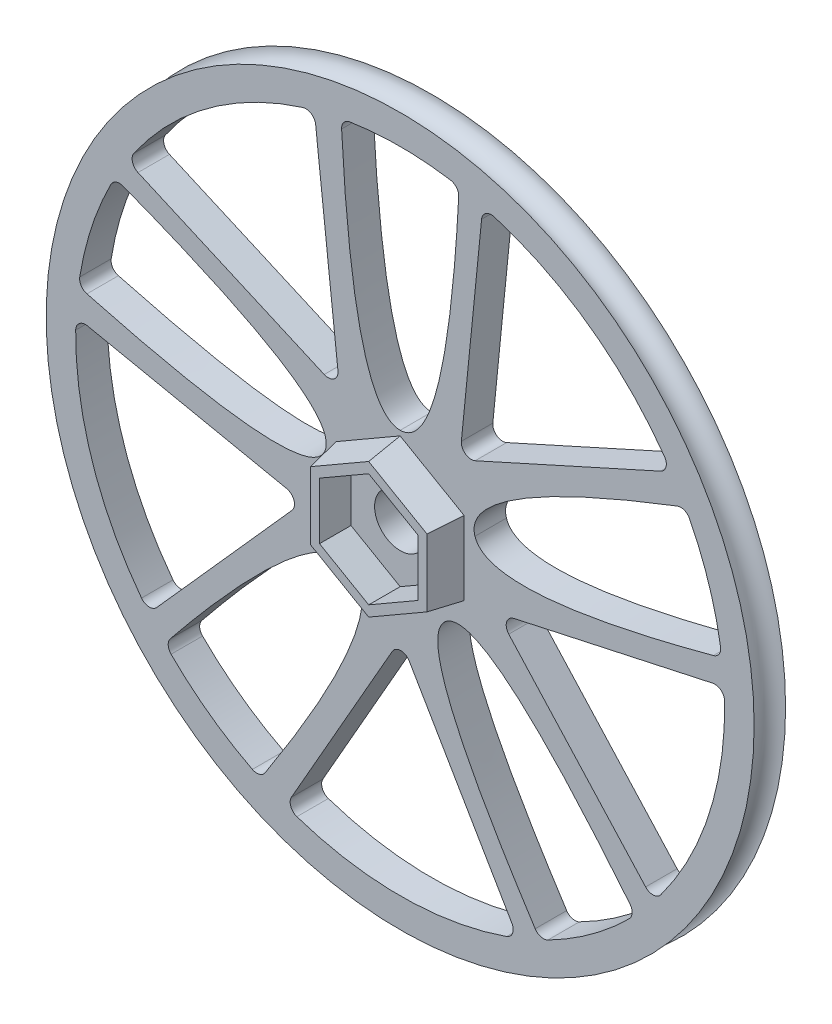
SolidWorks part; units mm, degrees
ref_plane "Front Plane" through (0, 0, 0) normal (0, 0, 1) x (1, 0, 0)
ref_plane "Top Plane" through (0, 0, 0) normal (0, 1, 0) x (1, 0, 0)
ref_plane "Right Plane" through (0, 0, 0) normal (1, 0, 0) x (0, 0, -1)
sketch "Sketch1" plane through (0, 0, 0) normal (0, 0, 1) x (1, 0, 0)
  circle A0 centre (0, 0) radius 45.72
  dimension "D1" = 91.44
extrude "Boss-Extrude1" add sketch "Sketch1" along normal mid plane 4.064
ref_axis "Axis1" through (0, 0, 17.7732) along (0, 0, -1)
sketch "Sketch2" plane through (0, 0, 0) normal (1, 0, 0) x (0, 0, -1)
  line L2 (-2.032, 45.72) -> (-2.032, -45.72) construction
  line L3 (-2.032, 45.72) -> (2.032, 45.72)
  circle A0 centre (0, 45.72) radius 2.032 construction
  arc A1 (-2.032, 45.72) -> (2.032, 45.72) centre (0, 45.72) ccw
revolve "Cut-Revolve1" cut sketch "Sketch2" angle 360 about axis through (0, 0, 17.7732) along (0, 0, -1)
sketch "Sketch3" plane through (0, 0, 0) normal (0, 0, 1) x (1, 0, 0)
  line L0 (0, 0) -> (0, 41.91) construction
  line L1 (0, 0) -> (41.91, 0) construction
  line L2 (-2.8815, 10.16) -> (2.8815, 10.16) construction
  line L3 (2.8814, 10.16) -> (-2.8815, 10.16) construction
  circle A0 centre (0, 0) radius 10.16 construction
  arc A1 (-7.62, 41.2115) -> (7.62, 41.2115) centre (0, 0) cw
  circle A2 centre (0, 0) radius 41.91 construction
  spline S0 degree 2 poles (0, 10.16) (6.0921, 10.16) (7.62, 41.2115) knots 0 0 0 1 1 1
  spline S1 degree 2 poles (0, 10.16) (-6.0921, 10.16) (-7.62, 41.2115) knots 0 0 0 1 1 1
  dimension "D1" = 20.32
  dimension "D2" = 83.82
  dimension "D3" = 15.24
extrude "Cut-Extrude1" cut sketch "Sketch3" against normal mid plane 5.08
pattern_circular "CirPattern1" count 5 over 360 about axis through (0, 0, 17.7732) along (0, 0, -1) of "Cut-Extrude1"
sketch "Sketch4" plane through (0, 0, 0) normal (0, 0, 1) x (1, 0, 0)
  line L0 (10.668, 40.5295) -> (7.6866, 10.6945)
  line L1 (7.6866, 10.6945) -> (35.0152, 23.0301)
  circle A0 centre (0, 0) radius 10.16 construction
  circle A1 centre (0, 0) radius 10.16 construction
  circle A2 centre (0, 0) radius 41.91 construction
  circle A3 centre (0, 0) radius 41.91 construction
  arc A4 (10.668, 40.5295) -> (35.0152, 23.0301) centre (0, 0) cw
  dimension "D1" = 3.048
  dimension "D2" = 3.048
  dimension "D3" = 60
extrude "Cut-Extrude2" cut sketch "Sketch4" against normal mid plane 5.08
pattern_circular "CirPattern2" count 5 over 360 about axis through (0, 0, 17.7732) along (0, 0, -1) of "Cut-Extrude2"
fillet "Fillet1" radius 1.27 25 edges at (-12.5047, -4.134, 0) (0.0675, -13.1701, 0) (12.5464, -4.0056, 0) (7.6866, 10.6945, 0) (-7.7958, 10.6152, 0) (10.668, 40.5295, 0) (35.0152, 23.0301, 0) (41.5491, 5.488, 0) (36.8397, 19.9821, 0) (41.8425, 2.3784, 0) (32.7232, -26.1847, 0) (30.3882, -28.8618, 0) (18.0588, -37.8197, 0) (15.1921, -39.0596, 0) (-14.7911, -39.2131, 0) (-18.0588, -37.8197, 0) (-30.3882, -28.8618, 0) (-32.4532, -26.5186, 0) (-41.8646, 1.9497, 0) (-41.5491, 5.488, 0) (-36.8397, 19.9821, 0) (-35.2493, 22.6702, 0) (-11.0826, 40.4181, 0) (-7.62, 41.2115, 0) (7.62, 41.2115, 0)
sketch "Sketch5" plane through (0, 0, 2.032) normal (0, 0, 1) x (1, 0, 0)
  line L1 (-8.255, -4.766) -> (0, -9.5321)
  line L2 (0, -9.5321) -> (8.255, -4.766)
  line L3 (8.255, -4.766) -> (8.255, 4.766)
  line L4 (8.255, 4.766) -> (0, 9.5321)
  line L5 (0, 9.5321) -> (-8.255, 4.766)
  line L6 (-8.255, 4.766) -> (-8.255, -4.766)
  line L7 (0, 0) -> (0, 41.91) construction
  circle A0 centre (0, 0) radius 8.255 construction
  dimension "D1" = 16.51
extrude "Boss-Extrude2" add sketch "Sketch5" along normal blind 4.064 draft 10
sketch "Sketch6" plane through (0, 0, 6.096) normal (0, 0, 1) x (1, 0, 0)
  line L0 (0, 0) -> (0, 41.91) construction
  line L1 (0, -7.3323) -> (6.35, -3.6662)
  line L2 (6.35, -3.6662) -> (6.35, 3.6662)
  line L3 (6.35, 3.6662) -> (0, 7.3323)
  line L4 (0, 7.3323) -> (-6.35, 3.6662)
  line L5 (-6.35, 3.6662) -> (-6.35, -3.6662)
  line L6 (-6.35, -3.6662) -> (0, -7.3323)
  circle A0 centre (0, 0) radius 6.35 construction
  dimension "D1" = 12.7
extrude "Cut-Extrude3" cut sketch "Sketch6" against normal up to surface (4.064 mm away) up to face at (-18.4542, 25.1283, 2.032)
sketch "Sketch7" plane through (0, 0, 2.032) normal (0, 0, 1) x (1, 0, 0)
  circle A0 centre (0, 0) radius 3.302
  dimension "D1" = 6.604
extrude "Cut-Extrude4" cut sketch "Sketch7" against normal up to next
